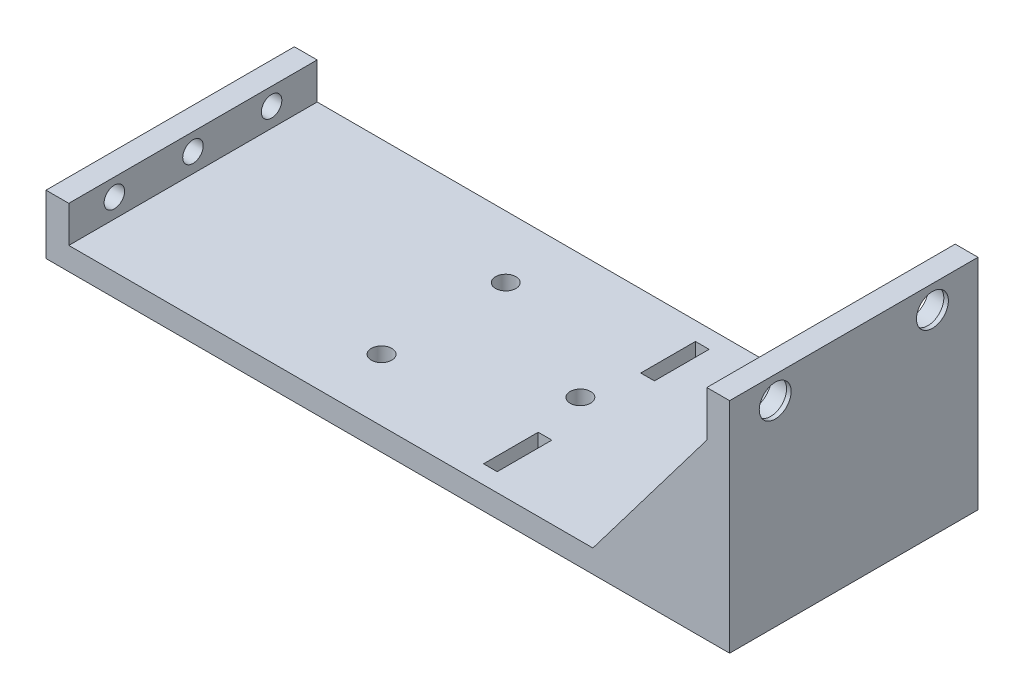
SolidWorks part; units mm, degrees
ref_plane "Front Plane" through (0, 0, 0) normal (0, 0, 1) x (1, 0, 0)
ref_plane "Top Plane" through (0, 0, 0) normal (0, 1, 0) x (1, 0, 0)
ref_plane "Right Plane" through (0, 0, 0) normal (1, 0, 0) x (0, 0, -1)
sketch "Sketch1" plane through (0, 0, 0) normal (0, 1, 0) x (1, 0, 0)
  line L2 (56.8875, -28.9394) -> (-93.1125, -28.9394)
  line L3 (56.8875, -28.9394) -> (56.8875, 25.5606)
  line L4 (56.8875, 25.5606) -> (-93.1125, 25.5606)
  line L5 (-93.1125, -28.9394) -> (-93.1125, 25.5606)
  dimension "D1" = 150
  dimension "D2" = 54.5
extrude "Boss-Extrude1" add sketch "Sketch1" along normal blind 5
sketch "Sketch2" plane through (0, 5, 0) normal (0, 1, 0) x (1, 0, 0)
  line L0 (-93.1125, -28.9394) -> (56.8875, -28.9394) construction
  line L1 (-93.1125, 25.5606) -> (-88.1125, 25.5606)
  line L2 (-93.1125, 25.5606) -> (-93.1125, -28.9394)
  line L3 (-93.1125, -28.9394) -> (-88.1125, -28.9394)
  line L4 (-88.1125, 25.5606) -> (-88.1125, -28.9394)
  dimension "D1" = 5
extrude "Boss-Extrude2" add sketch "Sketch2" along normal blind 8
hole_wizard "#8 Clearance Hole1" positions "3DSketch1" profile "Sketch3" hole size "#8" standard "ANSI Inch"
sketch3d "3DSketch1"
  line L1 (-93.1125, 13, -25.5606) -> (-93.1125, 13, 28.9394) construction
  line L2 (-93.1125, 13, -25.5606) -> (-93.1125, 0, -25.5606) construction
  line L3 (-93.1125, 13, 28.9394) -> (-93.1125, 0, 28.9394) construction
  point P0 (-93.1125, 9.2, -15.5606)
  point P2 (-93.1125, 9.2, 1.6894)
  point P4 (-93.1125, 9.2, 18.9394)
  dimension "D1" = 3.8
  dimension "D2" = 3.8
  dimension "D3" = 3.8
  dimension "D4" = 10
  dimension "D5" = 27.25
  dimension "D6" = 10
sketch "Sketch3" plane through (-93.1125, 9.2, -15.5606) normal (0, 1, 0) x (0, 0, 1)
  line L0 (0, 0) -> (0, 18.3507)
  line L1 (0, 18.3507) -> (2.2479, 17)
  line L2 (2.2479, 17) -> (2.2479, 0)
  line L5 (2.2479, 0) -> (0, 0)
  line L10 (0, 18.3507) -> (-2.2479, 17) construction
  line L11 (0, -6.35) -> (0, 107.95) construction
  dimension "Hole Dia." = 4.4958
  dimension "Hole Depth" = 17
  dimension "Drill Angle" = 118
sketch "Sketch7" plane through (0, 5, 0) normal (0, 1, 0) x (1, 0, 0)
  line L0 (56.8875, 25.5606) -> (-88.1125, 25.5606) construction
  line L1 (56.8875, -28.9394) -> (51.8875, -28.9394)
  line L2 (56.8875, -28.9394) -> (56.8875, 25.5606)
  line L3 (56.8875, 25.5606) -> (51.8875, 25.5606)
  line L4 (51.8875, -28.9394) -> (51.8875, 25.5606)
  dimension "D1" = 5
extrude "Boss-Extrude3" add sketch "Sketch7" along normal blind 43
sketch "Sketch8" plane through (51.8875, 0, 0) normal (-1, 0, 0) x (0, 0, 1)
  line L0 (-25.5606, 48) -> (28.9394, 48) construction
  line L1 (-25.5606, 48) -> (-25.5606, 5) construction
  line L2 (28.9394, 48) -> (28.9394, 5) construction
  circle A0 centre (-15.5606, 43) radius 4.25
  circle A1 centre (18.9394, 43) radius 4.25
  dimension "D1" = 8.5
  dimension "D2" = 8.5
  dimension "D3" = 5
  dimension "D4" = 5
  dimension "D5" = 10
  dimension "D6" = 10
extrude "Cut-Extrude1" cut sketch "Sketch8" against normal blind 4
sketch "Sketch10" plane through (0, 0, -25.5606) normal (0, 0, -1) x (-1, 0, 0)
  line L0 (-51.8875, 38) -> (-26.8875, 5)
  line L1 (-51.8875, 48) -> (-51.8875, 5) construction
  line L2 (-51.8875, 5) -> (88.1125, 5) construction
  dimension "D1" = 10
  dimension "D2" = 25
rib "Rib1" sketch "Sketch10" sketch "Sketch10" thickness 10 extrusion direction parallel to sketch draft on no parameters "D1"=10
sketch "Sketch12" plane through (0, 0, 28.9394) normal (0, 0, 1) x (1, 0, 0)
  line L0 (51.8875, 38) -> (26.8875, 5)
  line L1 (51.8875, 48) -> (51.8875, 5) construction
  line L2 (-88.1125, 5) -> (51.8875, 5) construction
  dimension "D1" = 10
  dimension "D2" = 25
rib "Rib3" sketch "Sketch12" sketch "Sketch12" thickness 10 extrusion direction parallel to sketch draft on no parameters "D1"=10
sketch "Sketch13" plane through (51.8875, 0, 0) normal (-1, 0, 0) x (0, 0, 1)
  line L0 (-25.5606, 48) -> (28.9394, 48) construction
  line L1 (-2.3106, 38) -> (5.6894, 38)
  line L2 (-2.3106, 38) -> (-2.3106, 36)
  line L3 (-2.3106, 36) -> (5.6894, 36)
  line L4 (5.6894, 38) -> (5.6894, 36)
  line L5 (-25.5606, 48) -> (-25.5606, 38) construction
  line L6 (28.9394, 48) -> (28.9394, 38) construction
  dimension "D1" = 8
  dimension "D2" = 10
  dimension "D3" = 23.25
  dimension "D4" = 23.25
  dimension "D5" = 2
extrude "Boss-Extrude4" add sketch "Sketch13" along normal blind 5
sketch "Sketch14" plane through (0, 38, 0) normal (0, 1, 0) x (1, 0, 0)
  line L0 (46.8875, -5.6894) -> (46.8875, 2.3106) construction
  line L1 (46.8875, 2.3106) -> (51.8875, 2.3106) construction
  circle A0 centre (49.3875, -1.6894) radius 2
  dimension "D1" = 2.5
  dimension "D2" = 4
extrude "Cut-Extrude2" cut sketch "Sketch14" against normal blind 2
sketch "Sketch15" plane through (55.8875, 0, 0) normal (-1, 0, 0) x (0, 0, 1)
  line L0 (28.9394, 48) -> (-25.5606, 48) construction
  circle A0 centre (-15.5606, 43) radius 3.5
  circle A1 centre (18.9394, 43) radius 3.5
  dimension "D1" = 5
  dimension "D2" = 5
extrude "Cut-Extrude3" cut sketch "Sketch15" against normal blind 1
sketch "Sketch16" plane through (0, 5, 0) normal (0, 1, 0) x (1, 0, 0)
  line L0 (56.8875, -28.9394) -> (56.8875, 25.5606) construction
  line L1 (1.8875, 21.5606) -> (-1.1125, 21.5606)
  line L2 (1.8875, 21.5606) -> (1.8875, 9.5606)
  line L3 (1.8875, 9.5606) -> (-1.1125, 9.5606)
  line L4 (-1.1125, 21.5606) -> (-1.1125, 9.5606)
  line L5 (26.8875, 25.5606) -> (-88.1125, 25.5606) construction
  line L6 (-88.1125, -28.9394) -> (26.8875, -28.9394) construction
  line L7 (1.8875, -12.9394) -> (-1.1125, -12.9394)
  line L8 (1.8875, -12.9394) -> (1.8875, -24.9394)
  line L9 (1.8875, -24.9394) -> (-1.1125, -24.9394)
  line L10 (-1.1125, -12.9394) -> (-1.1125, -24.9394)
  dimension "D1" = 55
  dimension "D2" = 12
  dimension "D3" = 3
  dimension "D4" = 4
  dimension "D5" = 12
  dimension "D6" = 4
  dimension "D7" = 55
  dimension "D8" = 3
extrude "Cut-Extrude4" cut sketch "Sketch16" against normal blind 5
hole_wizard "#8 Clearance Hole2" positions "3DSketch2" profile "Sketch17" hole size "#8" standard "ANSI Inch"
sketch3d "3DSketch2"
  line L1 (26.8875, 5, -25.5606) -> (-88.1125, 5, -25.5606) construction
  line L2 (-88.1125, 5, 28.9394) -> (26.8875, 5, 28.9394) construction
  line L5 (51.8875, 5, -15.5606) -> (51.8875, 5, 18.9394) construction
  point P0 (-3.1125, 5, 1.6894)
  point P2 (-33.1125, 5, 15.3144)
  point P4 (-33.1125, 5, -11.9356)
  dimension "D1" = 13.625
  dimension "D2" = 13.625
  dimension "D3" = 55
  dimension "D5" = 85
  dimension "D4" = 27.25
  dimension "D6" = 85
sketch "Sketch17" plane through (-3.1125, 5, 1.6894) normal (1, 0, 0) x (0, 0, 1)
  line L0 (0, 0) -> (0, 18.3507)
  line L1 (0, 18.3507) -> (2.2479, 17)
  line L2 (2.2479, 17) -> (2.2479, 0)
  line L5 (2.2479, 0) -> (0, 0)
  line L10 (0, 18.3507) -> (-2.2479, 17) construction
  line L11 (0, -6.35) -> (0, 107.95) construction
  dimension "Hole Dia." = 4.4958
  dimension "Hole Depth" = 17
  dimension "Drill Angle" = 118
